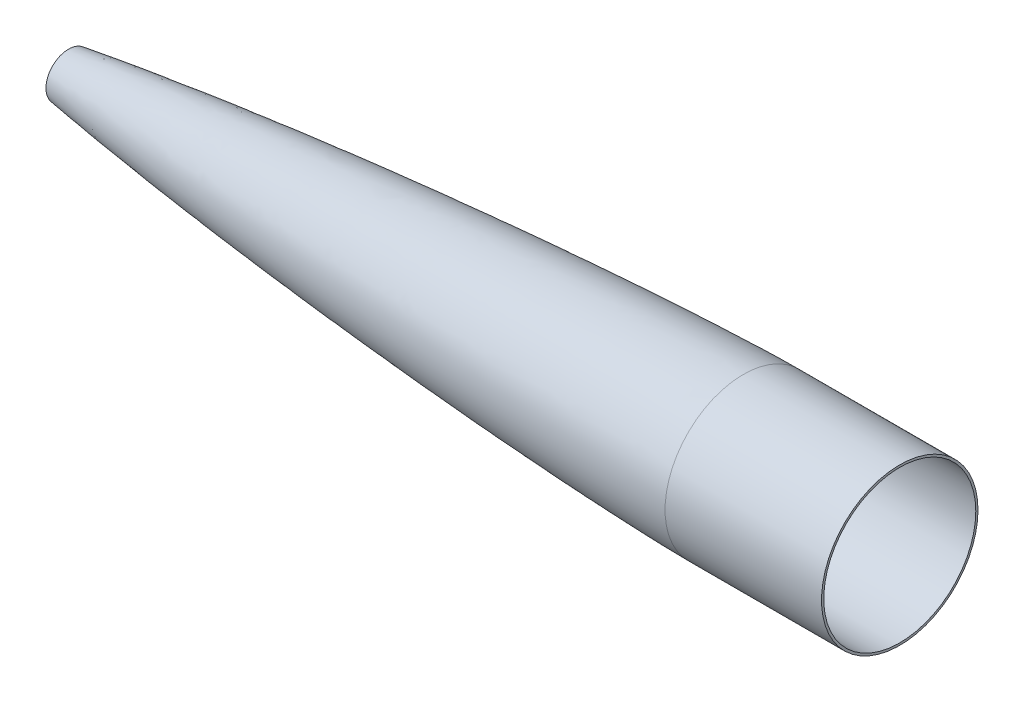
SolidWorks part; units mm, degrees
material "Fiberglass (correct density)"
ref_plane "Front Plane" through (0, 0, 0) normal (0, 0, 1) x (1, 0, 0)
ref_plane "Top Plane" through (0, 0, 0) normal (0, 1, 0) x (1, 0, 0)
ref_plane "Right Plane" through (0, 0, 0) normal (1, 0, 0) x (0, 0, -1)
ref_axis "Axis1" through (960.2211, 0, 0) along (-1, 0, 0)
sketch "Sketch1" plane through (0, 0, 0) normal (0, 0, 1) x (1, 0, 0)
  line L0 (762, 76.2) -> (914.4, 76.2)
  line L1 (762.0054, 74.041) -> (914.4, 74.041)
  line L2 (0, 0) -> (5.0002, 0)
  line L4 (960.2211, 0) -> (-47.8426, 0) construction
  line L5 (914.4, 76.2) -> (914.4, 74.041)
  spline S0 degree 4 poles (0, 0) (0.0027, 0.0075) (0.0093, 0.0218) (0.0273, 0.0478) (0.0695, 0.0948) (0.1335, 0.1534) (0.2203, 0.2218) (0.3436, 0.309) (0.4917, 0.4038) (0.6655, 0.506) (0.8652, 0.6153) (1.1559, 0.7654) (1.6068, 0.9816) (2.3724, 1.3169) (3.7418, 1.8559) (6.2093, 2.7173) (10.7438, 4.1026) (19.255, 6.352) (34.1072, 9.7183) (59.3412, 14.6384) (93.988, 20.4428) (135.9835, 26.6447) (182.6862, 32.8234) (229.4556, 38.469) (276.2762, 43.6717) (323.1379, 48.4889) (370.0344, 52.9546) (416.9611, 57.0901) (463.9149, 60.905) (510.8936, 64.4007) (557.8955, 67.5683) (604.9197, 70.3883) (646.0847, 72.5194) (681.3825, 74.0649) (709.847, 75.0891) (729.0089, 75.6493) (744.751, 76.0009) (754.6072, 76.1472) (759.5357, 76.1939) (762, 76.2) knots 0 0 0 0 0 0.000041 0.000082 0.000164 0.000329 0.000493 0.000658 0.000951 0.001245 0.001545 0.001844 0.002657 0.003853 0.005902 0.009516 0.016281 0.028569 0.051794 0.088907 0.150314 0.211721 0.273128 0.334535 0.395942 0.457348 0.518755 0.580162 0.641569 0.702976 0.764383 0.825789 0.887196 0.9179 0.948603 0.974302 0.987151 1 1 1 1 1 construction
  spline S1 degree 4 poles (0, 0) (0.0027, 0.0075) (0.0093, 0.0218) (0.0273, 0.0478) (0.0695, 0.0948) (0.1335, 0.1534) (0.2203, 0.2218) (0.3436, 0.309) (0.4917, 0.4038) (0.6655, 0.506) (0.8652, 0.6153) (1.1559, 0.7654) (1.6068, 0.9816) (2.3724, 1.3169) (3.7418, 1.8559) (6.2093, 2.7173) (10.7438, 4.1026) (19.255, 6.352) (34.1072, 9.7183) (59.3412, 14.6384) (93.988, 20.4428) (135.9835, 26.6447) (182.6862, 32.8234) (229.4556, 38.469) (276.2762, 43.6717) (323.1379, 48.4889) (370.0344, 52.9546) (416.9611, 57.0901) (463.9149, 60.905) (510.8936, 64.4007) (557.8955, 67.5683) (604.9197, 70.3883) (646.0847, 72.5194) (681.3825, 74.0649) (709.847, 75.0891) (729.0089, 75.6493) (744.751, 76.0009) (754.6072, 76.1472) (759.5357, 76.1939) (762, 76.2) knots 0 0 0 0 0 0.000041 0.000082 0.000164 0.000329 0.000493 0.000658 0.000951 0.001245 0.001545 0.001844 0.002657 0.003853 0.005902 0.009516 0.016281 0.028569 0.051794 0.088907 0.150314 0.211721 0.273128 0.334535 0.395942 0.457348 0.518755 0.580162 0.641569 0.702976 0.764383 0.825789 0.887196 0.9179 0.948603 0.974302 0.987151 1 1 1 1 1
  spline S2 degree 1 poles (1.5967, -1.4532) (762.0054, 74.041) knots 0 0 1 1 construction
  spline S3 degree 3 poles (1.5967, -1.4532) (1.6664, -1.4095) (1.798, -1.3339) (2.1594, -1.1452) (2.6519, -0.9164) (3.286, -0.6477) (4.0115, -0.3612) (4.6435, -0.127) (5.1132, 0.0404) (5.7203, 0.2534) (7.1381, 0.7304) (9.4593, 1.4465) (13.2491, 2.5246) (18.0389, 3.7657) (23.8307, 5.1477) (29.6486, 6.4486) (37.433, 8.0993) (47.1977, 10.0379) (58.9514, 12.2171) (70.7304, 14.2838) (82.5281, 16.2572) (98.2792, 18.7821) (117.999, 21.7696) (141.6975, 25.1414) (165.4237, 28.3342) (197.0881, 32.3865) (236.714, 37.1143) (284.3194, 42.3404) (331.9681, 47.1743) (379.6529, 51.6493) (427.369, 55.7855) (491.0273, 60.8586) (554.7356, 65.2733) (618.4862, 68.9559) (658.3468, 70.9123) (690.2433, 72.2265) (714.1699, 73.0646) (734.1074, 73.6176) (750.0615, 73.9267) (758.0225, 74.0311) (762.0054, 74.041) knots 0.000772 0.000772 0.000772 0.000772 0.00126 0.001748 0.002724 0.0037 0.004676 0.005971 0.006459 0.006703 0.008579 0.012482 0.016385 0.024192 0.031998 0.039805 0.047611 0.063224 0.078837 0.09445 0.110063 0.125676 0.156902 0.188128 0.219353 0.250579 0.313031 0.375483 0.437934 0.500386 0.562838 0.62529 0.750193 0.812645 0.875097 0.906322 0.937548 0.968774 0.984387 1 1 1 1 only from (5.0002, 0) to (762.0054, 74.041)
  dimension "D1" = 762
  dimension "D2" = 152.4
  dimension "D3" = 2.159
revolve "Revolve2" add sketch "Sketch1" angle 360 about axis through (960.2211, 0, 0) along (-1, 0, 0)
ref_plane "Plane1" through (104.775, 0, 0) normal (1, 0, 0) x (0, 0, -1)
split "Split1" trim tools "Plane1" bodies to split 101 resulting bodies 103
